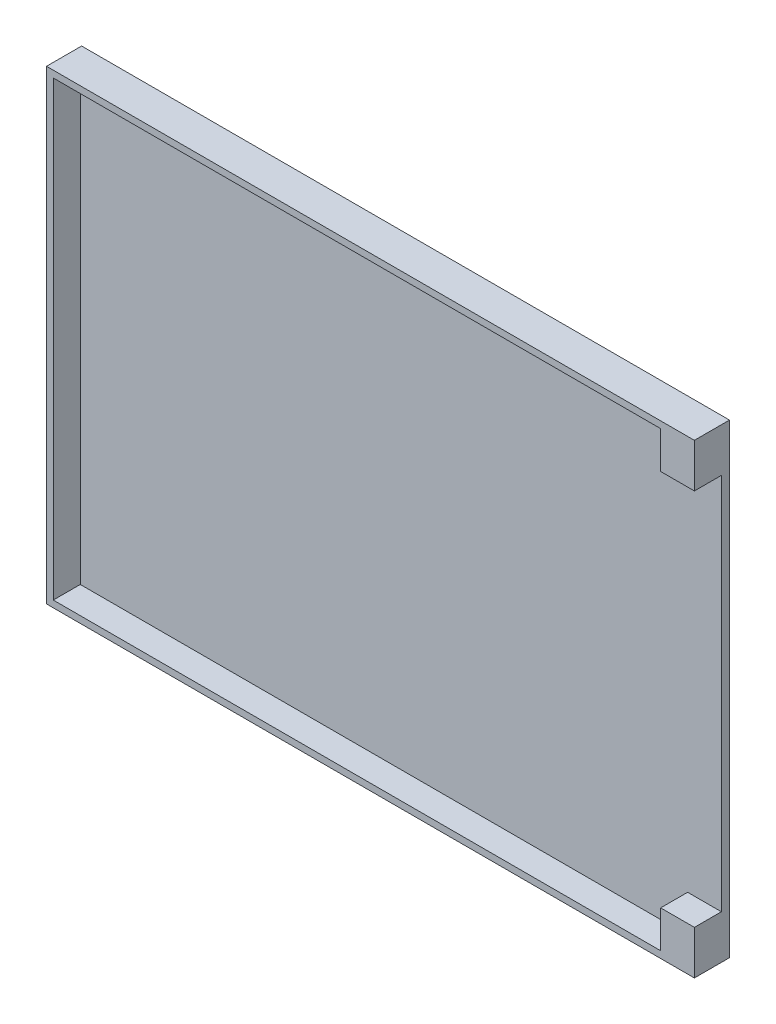
SolidWorks part; units mm, degrees
ref_plane "Спереди" through (0, 0, 0) normal (0, 0, 1) x (1, 0, 0)
ref_plane "Сверху" through (0, 0, 0) normal (0, 1, 0) x (1, 0, 0)
ref_plane "Справа" through (0, 0, 0) normal (1, 0, 0) x (0, 0, -1)
sketch "Эскиз1" plane through (0, 0, 0) normal (0, 0, 1) x (1, 0, 0)
  line L1 (-24, -17.25) -> (24, -17.25)
  line L2 (-24, -17.25) -> (-24, 17.25)
  line L3 (-24, 17.25) -> (24, 17.25)
  line L4 (24, -17.25) -> (24, 17.25)
  line L5 (-24, -17.25) -> (24, 17.25) construction
  line L6 (-24, 17.25) -> (24, -17.25) construction
  point P0 (0, 0)
  point P5 (-0.7716, 0)
  point P6 (0, 0)
  dimension "D1" = 34.5
  dimension "D2" = 48
extrude "Бобышка-Вытянуть1" add sketch "Эскиз1" along normal blind 0.6
sketch "Эскиз2" plane through (0, 0, 0.6) normal (0, 0, 1) x (1, 0, 0)
  line L4 (24, -17.25) -> (24, 17.25)
  line L5 (24, 17.25) -> (-24, 17.25)
  line L6 (-24, 17.25) -> (-24, -17.25)
  line L7 (-24, -17.25) -> (24, -17.25)
  line L9 (24, 17.25) -> (-24, 17.25)
  line L10 (-24, 17.25) -> (-24, -17.25)
  line L11 (-24, -17.25) -> (24, -17.25)
  line L12 (21.5, 16.75) -> (-23.5, 16.75)
  line L13 (-23.5, 16.75) -> (-23.5, -16.75)
  line L14 (-23.5, -16.75) -> (21.5, -16.75)
  line L15 (24, 16.75) -> (-23.5, 16.75) construction
  line L16 (-23.5, -16.75) -> (24, -16.75) construction
  line L17 (21.5, 16.75) -> (21.5, 14)
  line L18 (21.5, 14) -> (24, 14)
  line L19 (24, -17.25) -> (24, 17.25) construction
  line L20 (24, 14) -> (24, 17.25)
  line L21 (21.5, -16.75) -> (21.5, -14)
  line L22 (21.5, -14) -> (24, -14)
  line L23 (24, -14) -> (24, -17.25)
  point P8 (24, 12.8004)
  dimension "D3" = 2.5
  dimension "D4" = 3.25
  dimension "D1" = 0
  dimension "D2" = 0.5
extrude "Бобышка-Вытянуть2" add sketch "Эскиз2" along normal blind 2
